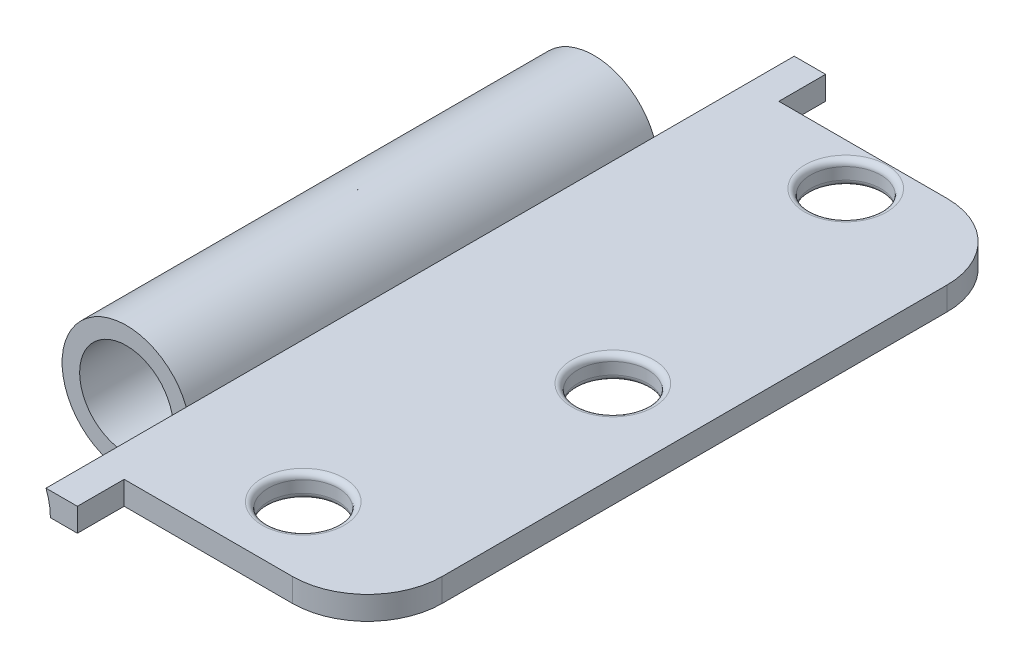
SolidWorks part; units mm, degrees
ref_plane "Front" through (0, 0, 0) normal (0, 0, 1) x (1, 0, 0)
ref_plane "Top" through (0, 0, 0) normal (0, 1, 0) x (1, 0, 0)
ref_plane "Right" through (0, 0, 0) normal (1, 0, 0) x (0, 0, -1)
sketch "Sketch1" plane through (0, 0, 0) normal (0, 1, 0) x (1, 0, 0)
  line L0 (0, 44.45) -> (0, -44.45)
  line L1 (0, -44.45) -> (23.2735, -44.45)
  line L2 (33.4335, -34.29) -> (33.4335, 34.29)
  line L3 (23.2735, 44.45) -> (0, 44.45)
  line L4 (15.209, 44.45) -> (15.209, -44.45) construction
  line L5 (15.209, 0) -> (33.4335, 0) construction
  arc A0 (23.2735, -44.45) -> (33.4335, -34.29) centre (23.2735, -34.29) ccw
  arc A1 (33.4335, 34.29) -> (23.2735, 44.45) centre (23.2735, 34.29) ccw
  circle A2 centre (15.209, 38.735) radius 4.7625
  circle A3 centre (15.209, -34.925) radius 4.7625
  circle A4 centre (22.321, 0) radius 4.7625
  point P3 (15.209, -30.1625)
  point P4 (0, 0)
  point P21 (15.209, 33.9725)
  point P22 (15.209, -39.6875)
  point P23 (27.0835, 0)
  point P24 (23.2735, -34.29)
  point P25 (19.9715, -34.925)
  dimension "D1" = 33.4335
  dimension "D3" = 10.16
  dimension "D4" = 9.525
  dimension "D5" = 64.135
  dimension "D2" = 88.9
  dimension "D6" = 4.7625
  dimension "D7" = 13.462
  dimension "D8" = 6.35
extrude "Boss-Extrude1" add sketch "Sketch1" along normal blind 3.175
sketch "Sketch2" plane through (0, 0, 44.45) normal (0, 0, 1) x (1, 0, 0)
  line L0 (0, 3.175) -> (23.2735, 3.175) construction
  line L1 (0, 0) -> (-3.251, 0)
  line L2 (0, 0) -> (0, 3.175)
  line L3 (0, 3.175) -> (-3.8487, 3.175)
  line L5 (-11.9822, 0) -> (0, 0) construction
  line L7 (-3.251, 0) -> (-5.6322, 0)
  line L8 (-3.8487, 3.175) -> (-6.4829, 3.175)
  arc A0 (-3.8487, 3.175) -> (-3.251, 0) centre (-11.9822, 0) ccw
  circle A1 centre (-11.9822, 0) radius 6.35
  point P3 (0, 1.5875)
  dimension "D1" = 17.4625
  dimension "D2" = 12.7
  dimension "D3" = 3.175
  dimension "D4" = 12.3957
extrude "Boss-Extrude2" add sketch "Sketch2" against normal offset from surface 6.35 and the other way blind 6.35 contours L2 A0 L1 | A0 region at (-2.9592, 1.625, 44.45) region at (-20.32, -1.5697, 44.45) up to face at (11.6368, 1.5875, -44.45) offset beyond the face yes
sketch "Sketch3" plane through (0, 0, 50.8) normal (0, 0, 1) x (1, 0, 0)
  circle A0 centre (-11.9822, 0) radius 8.7312
  arc A2 (-3.8487, 3.175) -> (-3.251, 0) centre (-11.9822, 0) ccw construction
extrude "Cut-Extrude2" [suppressed] cut sketch "Sketch3" against normal offset from surface (63.5 mm away) 19.05 from offset 19.05 offset against normal yes
sketch "Sketch4" plane through (0, 0, 50.8) normal (0, 0, 1) x (1, 0, 0)
  arc A0 (-3.8487, 3.175) -> (-3.251, 0) centre (-11.9822, 0) ccw construction
  circle A1 centre (-11.9822, 0) radius 8.7312
extrude "Cut-Extrude3" cut sketch "Sketch4" against normal blind 19.05
sketch "Sketch5" plane through (0, 0, -50.8) normal (0, 0, -1) x (-1, 0, 0)
  arc A0 (3.251, 0) -> (3.8487, 3.175) centre (11.9822, 0) ccw construction
  circle A1 centre (11.9822, 0) radius 8.7312
extrude "Cut-Extrude4" cut sketch "Sketch5" against normal blind 19.05
fillet "Fillet1" radius 0.7937 6 edges at (15.209, 0, 39.6875) (15.209, 0, -33.9725) (22.321, 0, 4.7625) (22.321, 3.175, 4.7625) (15.209, 3.175, -33.9725) (15.209, 3.175, 39.6875)
sketch "Sketch6" plane through (0, 0, 50.8) normal (0, 0, 1) x (1, 0, 0)
  line L0 (0, 0) -> (-3.251, 0) construction
  line L1 (0, 3.175) -> (0.4135, 3.175)
  line L2 (0, 3.175) -> (0, 0)
  line L3 (0, 0) -> (0.4135, 0)
  line L4 (0.4135, 3.175) -> (0.4135, 0)
  dimension "D1" = 0.4135
extrude "Boss-Extrude3" add sketch "Sketch6" against normal up to surface (101.6 mm away) up to face at (-1.7379, 1.5945, -50.8)
